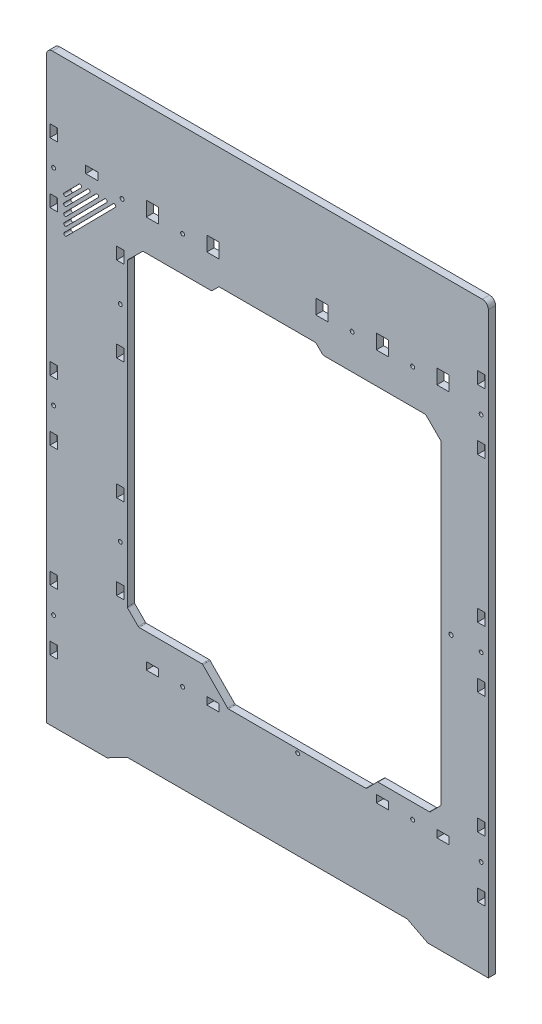
SolidWorks part; units mm, degrees
material "Клен"
ref_plane "Front" through (0, 0, 0) normal (0, 0, 1) x (1, 0, 0)
ref_plane "Top" through (0, 0, 0) normal (0, 1, 0) x (1, 0, 0)
ref_plane "Right" through (0, 0, 0) normal (1, 0, 0) x (0, 0, -1)
sketch "Эскиз1" plane through (0, 0, 0) normal (0, 0, 1) x (1, 0, 0)
  line L1 (768.3665, 485.0072) -> (768.3665, 477.0072)
  line L2 (745.3154, 525.0072) -> (1160.2565, 525.0072) construction
  line L3 (768.3665, 485.0072) -> (768.3665, 520.0072)
  line L4 (773.3665, 525.0072) -> (1128.3665, 525.0072)
  line L5 (1133.3665, 520.0072) -> (1133.3665, 485.0072)
  line L8 (1124.3665, 292.0072) -> (1130.4665, 292.0072)
  line L9 (1124.3665, 302.0072) -> (1124.3665, 292.0072)
  line L10 (1130.4665, 302.0072) -> (1124.3665, 302.0072)
  line L11 (1130.4665, 292.0072) -> (1130.4665, 302.0072)
  line L32 (1133.3665, 42.0072) -> (1133.3665, 477.0072)
  line L42 (768.3665, 477.0072) -> (768.3665, 42.0072)
  line L43 (768.3665, 42.0072) -> (818.3665, 42.0072)
  line L44 (818.3665, 42.0072) -> (835.3665, 50.7375)
  line L45 (835.3665, 50.7375) -> (1066.3665, 50.7375)
  line L46 (1066.3665, 50.7375) -> (1083.3665, 42.0072)
  line L47 (1083.3665, 42.0072) -> (1133.3665, 42.0072)
  line L48 (1124.3665, 242.0072) -> (1130.4665, 242.0072)
  line L49 (1124.3665, 252.0072) -> (1124.3665, 242.0072)
  line L50 (1130.4665, 252.0072) -> (1124.3665, 252.0072)
  line L51 (1130.4665, 242.0072) -> (1130.4665, 252.0072)
  line L56 (1124.3665, 142.0072) -> (1130.4665, 142.0072)
  line L57 (1124.3665, 152.0072) -> (1124.3665, 142.0072)
  line L58 (1130.4665, 152.0072) -> (1124.3665, 152.0072)
  line L59 (1130.4665, 142.0072) -> (1130.4665, 152.0072)
  line L64 (1124.3665, 92.0072) -> (1130.4665, 92.0072)
  line L65 (1124.3665, 102.0072) -> (1124.3665, 92.0072)
  line L66 (1130.4665, 102.0072) -> (1124.3665, 102.0072)
  line L67 (1130.4665, 92.0072) -> (1130.4665, 102.0072)
  line L72 (1100.8665, 127.1049) -> (1090.8665, 127.1049)
  line L73 (1100.8665, 121.0049) -> (1100.8665, 127.1049)
  line L74 (1090.8665, 121.0049) -> (1100.8665, 121.0049)
  line L75 (1090.8665, 127.1049) -> (1090.8665, 121.0049)
  line L80 (1050.8665, 127.1049) -> (1040.8665, 127.1049)
  line L81 (1050.8665, 121.0049) -> (1050.8665, 127.1049)
  line L82 (1040.8665, 121.0049) -> (1050.8665, 121.0049)
  line L83 (1040.8665, 127.1049) -> (1040.8665, 121.0049)
  line L96 (910.8665, 121.0049) -> (910.8665, 127.1049)
  line L97 (900.8665, 121.0049) -> (910.8665, 121.0049)
  line L98 (900.8665, 127.1049) -> (900.8665, 121.0049)
  line L99 (910.8665, 127.1049) -> (900.8665, 127.1049)
  line L104 (860.8665, 121.0049) -> (860.8665, 127.1049)
  line L105 (850.8665, 121.0049) -> (860.8665, 121.0049)
  line L106 (850.8665, 127.1049) -> (850.8665, 121.0049)
  line L107 (860.8665, 127.1049) -> (850.8665, 127.1049)
  line L112 (771.2665, 102.0072) -> (771.2665, 92.0072)
  line L113 (777.3665, 102.0072) -> (771.2665, 102.0072)
  line L114 (777.3665, 92.0072) -> (777.3665, 102.0072)
  line L115 (771.2665, 92.0072) -> (777.3665, 92.0072)
  line L120 (771.2665, 152.0072) -> (771.2665, 142.0072)
  line L121 (777.3665, 152.0072) -> (771.2665, 152.0072)
  line L122 (777.3665, 142.0072) -> (777.3665, 152.0072)
  line L123 (771.2665, 142.0072) -> (777.3665, 142.0072)
  line L128 (826.3665, 172.0072) -> (826.3665, 162.0072)
  line L129 (832.4665, 172.0072) -> (826.3665, 172.0072)
  line L130 (832.4665, 162.0072) -> (832.4665, 172.0072)
  line L131 (826.3665, 162.0072) -> (832.4665, 162.0072)
  line L136 (826.3665, 242.0072) -> (826.3665, 232.0072)
  line L137 (832.4665, 242.0072) -> (826.3665, 242.0072)
  line L138 (832.4665, 232.0072) -> (832.4665, 242.0072)
  line L139 (826.3665, 232.0072) -> (832.4665, 232.0072)
  line L144 (771.2665, 252.0072) -> (771.2665, 242.0072)
  line L145 (777.3665, 252.0072) -> (771.2665, 252.0072)
  line L146 (777.3665, 242.0072) -> (777.3665, 252.0072)
  line L147 (771.2665, 242.0072) -> (777.3665, 242.0072)
  line L152 (1124.3665, 412.0072) -> (1130.4665, 412.0072)
  line L153 (1124.3665, 422.0072) -> (1124.3665, 412.0072)
  line L154 (1130.4665, 422.0072) -> (1124.3665, 422.0072)
  line L155 (1130.4665, 412.0072) -> (1130.4665, 422.0072)
  line L160 (1124.3665, 462.0072) -> (1130.4665, 462.0072)
  line L161 (1124.3665, 472.0072) -> (1124.3665, 462.0072)
  line L162 (1130.4665, 472.0072) -> (1124.3665, 472.0072)
  line L163 (1130.4665, 462.0072) -> (1130.4665, 472.0072)
  line L168 (1090.8665, 457.1072) -> (1090.8665, 445.0072)
  line L169 (1100.8665, 457.1072) -> (1090.8665, 457.1072)
  line L170 (1100.8665, 445.0072) -> (1100.8665, 457.1072)
  line L171 (1090.8665, 445.0072) -> (1100.8665, 445.0072)
  line L176 (1040.8665, 457.1072) -> (1040.8665, 445.0072)
  line L177 (1050.8665, 457.1072) -> (1040.8665, 457.1072)
  line L178 (1050.8665, 445.0072) -> (1050.8665, 457.1072)
  line L179 (1040.8665, 445.0072) -> (1050.8665, 445.0072)
  line L184 (990.8665, 457.1072) -> (990.8665, 445.0072)
  line L185 (1000.8665, 457.1072) -> (990.8665, 457.1072)
  line L186 (1000.8665, 445.0072) -> (1000.8665, 457.1072)
  line L187 (990.8665, 445.0072) -> (1000.8665, 445.0072)
  line L192 (900.8665, 445.0072) -> (910.8665, 445.0072)
  line L193 (900.8665, 457.1072) -> (900.8665, 445.0072)
  line L194 (910.8665, 457.1072) -> (900.8665, 457.1072)
  line L195 (910.8665, 445.0072) -> (910.8665, 457.1072)
  line L200 (826.3665, 412.0072) -> (826.3665, 402.0072)
  line L201 (832.4665, 412.0072) -> (826.3665, 412.0072)
  line L202 (832.4665, 402.0072) -> (832.4665, 412.0072)
  line L203 (826.3665, 402.0072) -> (832.4665, 402.0072)
  line L224 (996.2808, 419.7551) -> (991.4523, 424.5835)
  line L225 (1081.1223, 419.1693) -> (997.695, 419.1693)
  line L226 (1094.1201, 406.6723) -> (1081.8269, 418.8789)
  line L227 (1094.4155, 146.42) -> (1094.4155, 405.9627)
  line L228 (1085.3572, 136.8536) -> (1094.1263, 145.7167)
  line L229 (1042.289, 136.5569) -> (1084.6463, 136.5569)
  line L230 (1032.8134, 127.4016) -> (1041.5781, 136.2603)
  line L231 (918.729, 127.1049) -> (1032.1025, 127.1049)
  line L232 (897.5745, 148.2016) -> (918.0158, 127.4039)
  line L233 (844.9385, 148.5006) -> (896.8613, 148.5006)
  line L234 (835.4584, 157.6604) -> (844.2276, 148.7973)
  line L235 (835.1693, 405.9627) -> (835.1693, 158.3637)
  line L236 (847.7579, 418.8789) -> (835.4647, 406.6723)
  line L237 (904.0381, 419.1693) -> (848.4625, 419.1693)
  line L238 (910.2808, 424.5835) -> (905.4523, 419.7551)
  line L239 (990.0381, 425.1693) -> (911.695, 425.1693)
  line L240 (850.8665, 445.0072) -> (860.8665, 445.0072)
  line L241 (850.8665, 457.1072) -> (850.8665, 445.0072)
  line L242 (860.8665, 457.1072) -> (850.8665, 457.1072)
  line L243 (860.8665, 445.0072) -> (860.8665, 457.1072)
  line L244 (784.8721, 398.2711) -> (825.3055, 439.1538)
  line L245 (823.528, 440.9118) -> (783.0946, 400.0291)
  line L248 (784.8331, 405.3421) -> (818.2346, 439.1147)
  line L249 (816.4571, 440.8727) -> (783.0556, 407.1001)
  line L252 (784.794, 412.4131) -> (811.1636, 439.0757)
  line L253 (809.3861, 440.8336) -> (783.0165, 414.171)
  line L256 (784.7549, 419.484) -> (804.0927, 439.0366)
  line L257 (802.3151, 440.7946) -> (782.9774, 421.242)
  line L260 (784.7159, 426.555) -> (797.0217, 438.9975)
  line L261 (795.2442, 440.7555) -> (782.9384, 428.313)
  line L263 (1133.3665, 485.0072) -> (1133.3665, 477.0072)
  line L268 (771.2665, 422.0072) -> (771.2665, 412.0072)
  line L269 (777.3665, 422.0072) -> (771.2665, 422.0072)
  line L270 (777.3665, 412.0072) -> (777.3665, 422.0072)
  line L271 (771.2665, 412.0072) -> (777.3665, 412.0072)
  line L276 (800.8665, 451.0072) -> (810.8665, 451.0072)
  line L277 (800.8665, 457.1072) -> (800.8665, 451.0072)
  line L278 (810.8665, 457.1072) -> (800.8665, 457.1072)
  line L279 (810.8665, 451.0072) -> (810.8665, 457.1072)
  line L284 (771.2665, 472.0072) -> (771.2665, 462.0072)
  line L285 (777.3665, 472.0072) -> (771.2665, 472.0072)
  line L286 (777.3665, 462.0072) -> (777.3665, 472.0072)
  line L287 (771.2665, 462.0072) -> (777.3665, 462.0072)
  line L292 (826.3665, 342.0072) -> (826.3665, 332.0072)
  line L293 (832.4665, 342.0072) -> (826.3665, 342.0072)
  line L294 (832.4665, 332.0072) -> (832.4665, 342.0072)
  line L295 (826.3665, 332.0072) -> (832.4665, 332.0072)
  line L300 (771.2665, 302.0072) -> (771.2665, 292.0072)
  line L301 (777.3665, 302.0072) -> (771.2665, 302.0072)
  line L302 (777.3665, 292.0072) -> (777.3665, 302.0072)
  line L303 (771.2665, 292.0072) -> (777.3665, 292.0072)
  arc A1 (1128.3665, 525.0072) -> (1133.3665, 520.0072) centre (1128.3665, 520.0072) cw
  circle A2 centre (1127.4165, 272.0072) radius 1.6
  arc A3 (768.3665, 520.0072) -> (773.3665, 525.0072) centre (773.3665, 520.0072) cw
  circle A4 centre (1102.521, 272.0072) radius 1.7
  circle A6 centre (1127.4165, 122.0072) radius 1.6
  circle A24 centre (1070.8665, 124.0549) radius 1.6
  circle A26 centre (975.8665, 124.0549) radius 1.6
  circle A28 centre (880.8665, 124.0549) radius 1.6
  circle A38 centre (774.3165, 122.0072) radius 1.6
  circle A40 centre (829.4165, 202.0072) radius 1.6
  circle A42 centre (774.3165, 272.0072) radius 1.6
  circle A44 centre (1127.4165, 442.0072) radius 1.6
  circle A46 centre (1070.8665, 448.0572) radius 1.6
  circle A48 centre (1020.8665, 448.0572) radius 1.6
  circle A50 centre (880.8665, 448.0572) radius 1.6
  circle A52 centre (830.8665, 448.0572) radius 1.6
  arc A56 (825.3055, 439.1538) -> (823.528, 440.9118) centre (824.4168, 440.0328) ccw
  arc A57 (783.0946, 400.0291) -> (784.8721, 398.2711) centre (783.9834, 399.1501) ccw
  arc A60 (818.2346, 439.1147) -> (816.4571, 440.8727) centre (817.3458, 439.9937) ccw
  arc A61 (783.0556, 407.1001) -> (784.8331, 405.3421) centre (783.9443, 406.2211) ccw
  arc A64 (811.1636, 439.0757) -> (809.3861, 440.8336) centre (810.2749, 439.9546) ccw
  arc A65 (783.0165, 414.171) -> (784.794, 412.4131) centre (783.9053, 413.292) ccw
  arc A82 (991.4523, 424.5835) -> (990.0381, 425.1693) centre (990.0381, 423.1693) ccw
  arc A83 (996.2808, 419.7551) -> (997.695, 419.1693) centre (997.695, 421.1693) ccw
  arc A84 (1081.8269, 418.8789) -> (1081.1223, 419.1693) centre (1081.1223, 418.1693) ccw
  arc A85 (1094.4155, 405.9627) -> (1094.1201, 406.6723) centre (1093.4155, 405.9627) ccw
  arc A86 (1094.1263, 145.7167) -> (1094.4155, 146.42) centre (1093.4155, 146.42) ccw
  arc A87 (1084.6463, 136.5569) -> (1085.3572, 136.8536) centre (1084.6463, 137.5569) ccw
  arc A88 (1042.289, 136.5569) -> (1041.5781, 136.2603) centre (1042.289, 135.5569) ccw
  arc A89 (1032.1025, 127.1049) -> (1032.8134, 127.4016) centre (1032.1025, 128.1049) ccw
  arc A90 (918.0158, 127.4039) -> (918.729, 127.1049) centre (918.729, 128.1049) ccw
  arc A91 (897.5745, 148.2016) -> (896.8613, 148.5006) centre (896.8613, 147.5006) ccw
  arc A92 (844.2276, 148.7973) -> (844.9385, 148.5006) centre (844.9385, 149.5006) ccw
  arc A93 (835.1693, 158.3637) -> (835.4584, 157.6604) centre (836.1693, 158.3637) ccw
  arc A94 (835.4647, 406.6723) -> (835.1693, 405.9627) centre (836.1693, 405.9627) ccw
  arc A95 (848.4625, 419.1693) -> (847.7579, 418.8789) centre (848.4625, 418.1693) ccw
  arc A96 (904.0381, 419.1693) -> (905.4523, 419.7551) centre (904.0381, 421.1693) ccw
  arc A97 (911.695, 425.1693) -> (910.2808, 424.5835) centre (911.695, 423.1693) ccw
  arc A100 (804.0927, 439.0366) -> (802.3151, 440.7946) centre (803.2039, 439.9156) ccw
  arc A101 (782.9774, 421.242) -> (784.7549, 419.484) centre (783.8662, 420.363) ccw
  arc A104 (797.0217, 438.9975) -> (795.2442, 440.7555) centre (796.1329, 439.8765) ccw
  arc A105 (782.9384, 428.313) -> (784.7159, 426.555) centre (783.8271, 427.434) ccw
  circle A106 centre (774.3165, 442.0072) radius 1.6
  circle A108 centre (829.4165, 372.0072) radius 1.6
  point P10 (1133.3665, 525.0072)
  point P14 (768.3665, 525.0072)
  dimension "D1" = 5
extrude "Бобышка-Вытянуть1" add sketch "Эскиз1" along normal blind 6 contours L1 L42 L43 L44 L45 L46 L47 L32 L263 L11 L8 L9 L10 L51 L48 L49 L50 L59 L56 L57 L58 L67 L64 L65 L66 L75 L72 L73 L74 L83 L80 L81 L82 L99 L96 L97 L98 region at (774.4206, 502.5072, 0)
